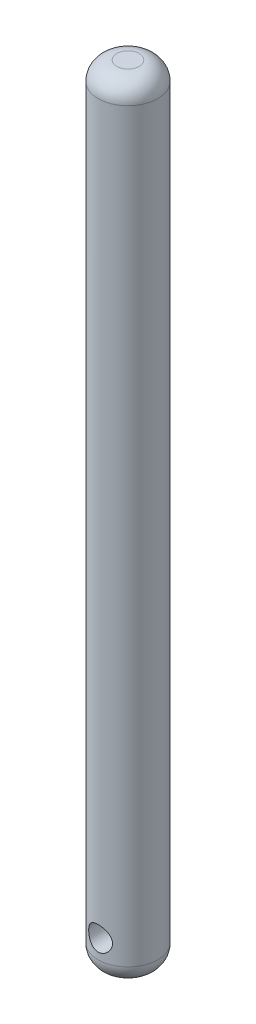
SolidWorks part; units mm, degrees
ref_plane "Front Plane" through (0, 0, 0) normal (0, 0, 1) x (1, 0, 0)
ref_plane "Top Plane" through (0, 0, 0) normal (0, 1, 0) x (1, 0, 0)
ref_plane "Right Plane" through (0, 0, 0) normal (1, 0, 0) x (0, 0, -1)
sketch "Sketch1" plane through (0, 0, 0) normal (0, 1, 0) x (1, 0, 0)
  circle A0 centre (0, 0) radius 4
  dimension "D1" = 8
extrude "Boss-Extrude1" add sketch "Sketch1" along normal blind 105
sketch "Sketch2" plane through (0, 0, 0) normal (0, 0, 1) x (1, 0, 0)
  circle A0 centre (0, 5) radius 1.6
  dimension "D1" = 3.2
  dimension "D2" = 5
extrude "Cut-Extrude1" cut sketch "Sketch2" against normal through all both and the other way through all
sketch "Sketch3" plane through (0, 0, 0) normal (0, 0, 1) x (1, 0, 0)
  circle A0 centre (0, 5) radius 3
  dimension "D1" = 6
extrude "Cut-Extrude2" cut sketch "Sketch3" against normal up to next from offset 1 offset against normal yes
fillet "Fillet1" radius 2.5 2 edges at (0, 0, 4) (0, 105, 4)
